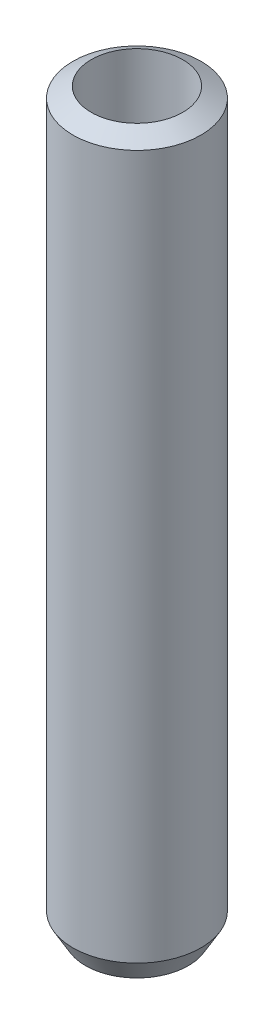
SolidWorks part; units mm, degrees
ref_plane "Front Plane" through (0, 0, 0) normal (0, 0, 1) x (1, 0, 0)
ref_plane "Top Plane" through (0, 0, 0) normal (0, 1, 0) x (1, 0, 0)
ref_plane "Right Plane" through (0, 0, 0) normal (1, 0, 0) x (0, 0, -1)
sketch "Sketch1" plane through (0, 0, 0) normal (0, 1, 0) x (1, 0, 0)
  circle A0 centre (0, 0) radius 27.5
  dimension "SHAFT_OD" = 55
extrude "Boss-Extrude1" add sketch "Sketch1" along normal blind 317.2156
sketch "Sketch2" plane through (0, 0, 0) normal (0, 1, 0) x (1, 0, 0)
  circle A0 centre (0, 0) radius 19.6586
  dimension "BORE_D" = 39.3172
extrude "Cut-Extrude1" cut sketch "Sketch2" along normal through all
chamfer "Chamfer1" distance 5.3903 angle 60 2 edges at (0, 317.2156, 27.5) (0, 0, 27.5) first distance on face at (0, 317.2156, 27.5) first distance on face at (0, 0, 19.6586)
